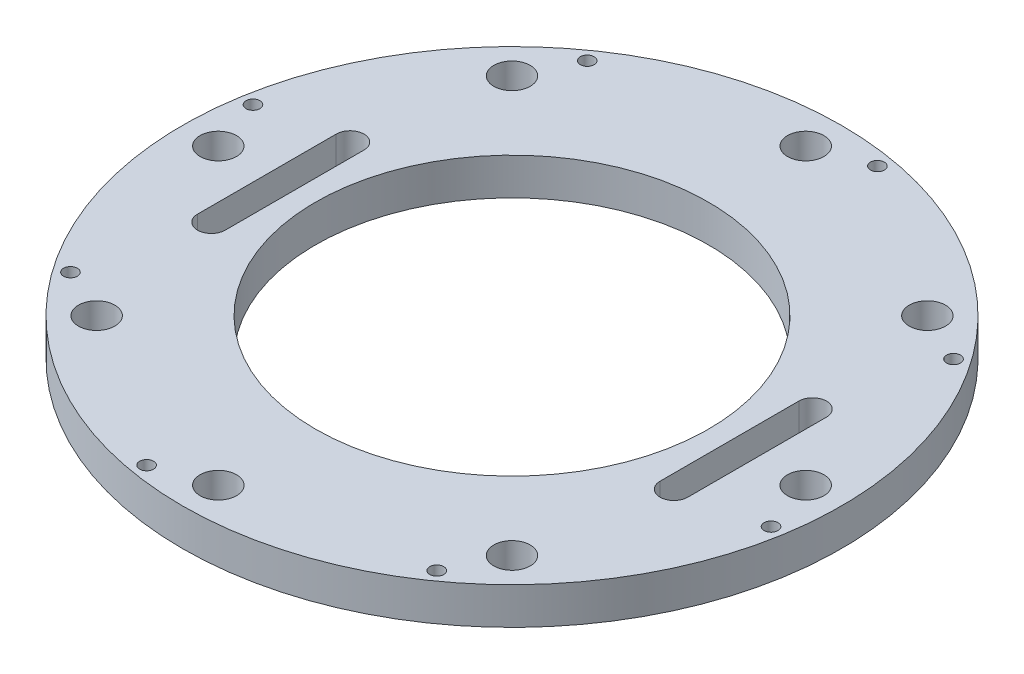
SolidWorks part; units mm, degrees
ref_plane "Front Plane" through (0, 0, 0) normal (0, 0, 1) x (1, 0, 0)
ref_plane "Top Plane" through (0, 0, 0) normal (0, 1, 0) x (1, 0, 0)
ref_plane "Right Plane" through (0, 0, 0) normal (1, 0, 0) x (0, 0, -1)
sketch "Sketch1" plane through (0, 0, 0) normal (0, 1, 0) x (1, 0, 0)
  line L0 (10, -3) -> (10, 3) construction
  line L1 (9.4, -3) -> (9.4, 3)
  line L2 (10.6, -3) -> (10.6, 3)
  line L3 (0, 0) -> (0, -14.25) construction
  line L4 (-10, -3) -> (-10, 3) construction
  line L5 (-9.4, -3) -> (-9.4, 3)
  line L6 (-10.6, -3) -> (-10.6, 3)
  line L7 (0, 0) -> (-13.1653, 5.4532) construction
  line L8 (0, 0) -> (-14.25, 0) construction
  circle A0 centre (0, 0) radius 14.25
  circle A1 centre (0, 0) radius 8.5
  arc A2 (9.4, -3) -> (10.6, -3) centre (10, -3) ccw
  arc A3 (10.6, 3) -> (9.4, 3) centre (10, 3) ccw
  arc A4 (-9.4, -3) -> (-10.6, -3) centre (-10, -3) cw
  arc A5 (-10.6, 3) -> (-9.4, 3) centre (-10, 3) cw
  circle A7 centre (-8.9803, -8.9803) radius 0.7874
  circle A8 centre (-12.7, 0) radius 0.7874
  circle A9 centre (-8.9803, 8.9803) radius 0.7874
  circle A10 centre (0, 12.7) radius 0.7874
  circle A11 centre (8.9803, 8.9803) radius 0.7874
  circle A12 centre (12.7, 0) radius 0.7874
  circle A13 centre (8.9803, -8.9803) radius 0.7874
  circle A14 centre (0, -12.7) radius 0.7874
  circle A15 centre (-13.5, 2.3) radius 0.3
  circle A17 centre (-7.9196, 11.1723) radius 0.3
  circle A18 centre (2.3, 13.5) radius 0.3
  circle A19 centre (11.1723, 7.9196) radius 0.3
  circle A20 centre (13.5, -2.3) radius 0.3
  circle A21 centre (7.9196, -11.1723) radius 0.3
  circle A22 centre (-2.3, -13.5) radius 0.3
  circle A23 centre (-11.1723, -7.9196) radius 0.3
  point P6 (10, 0)
  point P13 (-10, 0)
  point P38 (0, 0)
  point P44 (0, 0)
  point P58 (0, 0)
  point P61 (0, 0)
  dimension "D1" = 8
  dimension "D2" = 17
  dimension "D6" = 12.7
  dimension "D7" = 1.5748
  dimension "D12" = 0.6
  dimension "D3" = 1.2
  dimension "D4" = 6
  dimension "D5" = 10
  dimension "D8" = 12.7
  dimension "D9" = 8.9803
  dimension "D10" = 2.3
  dimension "D11" = 13.5
  dimension "D13" = 22.5
  dimension "D14" = 8
extrude "Boss-Extrude1" add sketch "Sketch1" along normal blind 1.6 contours A0 A3 L2 A2 L1 A1 L6 A5 L5 A4 region at (-13.8469, 0, 0)
